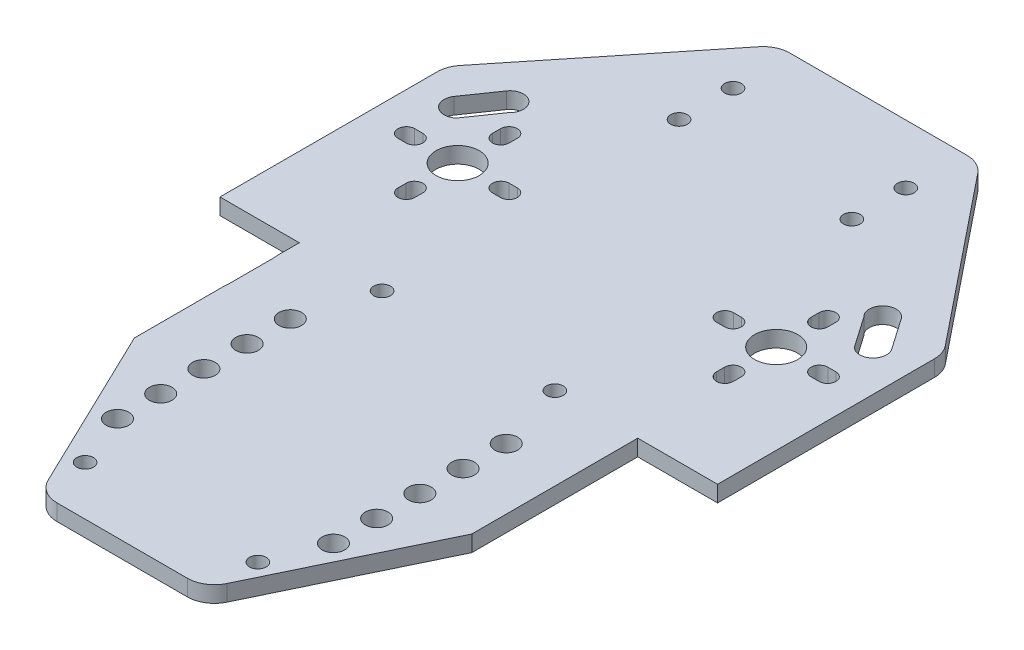
SolidWorks part; units mm, degrees
material "Thornel Mat VMA"
ref_plane "Front Plane" through (0, 0, 0) normal (0, 0, 1) x (1, 0, 0)
ref_plane "Top Plane" through (0, 0, 0) normal (0, 1, 0) x (1, 0, 0)
ref_plane "Right Plane" through (0, 0, 0) normal (1, 0, 0) x (0, 0, -1)
sketch "Sketch1" plane through (0, 0, 0) normal (0, 1, 0) x (1, 0, 0)
  line L0 (0, 0) -> (0, -27.5) construction
  line L1 (0, 0) -> (121.6069, 0) construction
  line L2 (37.5, 0) -> (39, 0) construction
  line L3 (37.5, 1.55) -> (39, 1.55)
  line L4 (37.5, -1.55) -> (39, -1.55)
  line L5 (29.5, -8) -> (29.5, -9.5) construction
  line L6 (31.05, -8) -> (31.05, -9.5)
  line L7 (27.95, -8) -> (27.95, -9.5)
  line L8 (21.5, 0) -> (20, 0) construction
  line L9 (21.5, -1.55) -> (20, -1.55)
  line L10 (21.5, 1.55) -> (20, 1.55)
  line L11 (29.5, 8) -> (29.5, 9.5) construction
  line L12 (27.95, 8) -> (27.95, 9.5)
  line L13 (31.05, 8) -> (31.05, 9.5)
  line L14 (20, -72.5) -> (20, -64.5) construction
  line L19 (-29.5, 8) -> (-29.5, 9.5) construction
  line L20 (-27.95, 8) -> (-27.95, 9.5)
  line L21 (-31.05, 8) -> (-31.05, 9.5)
  line L22 (-21.5, 0) -> (-20, 0) construction
  line L23 (-21.5, -1.55) -> (-20, -1.55)
  line L24 (-21.5, 1.55) -> (-20, 1.55)
  line L25 (-29.5, -8) -> (-29.5, -9.5) construction
  line L26 (-31.05, -8) -> (-31.05, -9.5)
  line L27 (-27.95, -8) -> (-27.95, -9.5)
  line L28 (-37.5, 0) -> (-39, 0) construction
  line L29 (-37.5, 1.55) -> (-39, 1.55)
  line L30 (-37.5, -1.55) -> (-39, -1.55)
  line L31 (-31.3246, -40.5321) -> (-31.3246, -32.4375)
  line L34 (-38.4806, -33.6183) -> (-38.4806, -40.5321)
  line L35 (31.3246, -40.5321) -> (31.3246, -32.4375)
  line L36 (38.4806, -33.6183) -> (38.4806, -40.5321)
  line L37 (-36.8266, 7.1221) -> (-32.8384, 12.8748)
  line L38 (29.5, 0) -> (50.8627, -25.4591) construction
  line L41 (46, 48.4159) -> (-46, 48.4159)
  line L44 (46, 48.4159) -> (46.1488, -91.633)
  line L47 (46.1488, -91.633) -> (-46.1487, -91.584)
  line L50 (-46, 48.4159) -> (-46.1487, -91.584)
  line L53 (-36.5402, 16.1211) -> (-40.5285, 10.3684)
  line L59 (-959, -57) -> (49041, -57) construction
  line L63 (36.8266, 7.1221) -> (32.8384, 12.8748)
  line L64 (36.5402, 16.1211) -> (40.5285, 10.3684)
  circle A0 centre (29.5, 0) radius 4
  arc A1 (37.5, 1.55) -> (37.5, -1.55) centre (37.5, 0) ccw
  arc A2 (39, -1.55) -> (39, 1.55) centre (39, 0) ccw
  arc A3 (31.05, -8) -> (27.95, -8) centre (29.5, -8) ccw
  arc A4 (27.95, -9.5) -> (31.05, -9.5) centre (29.5, -9.5) ccw
  arc A5 (21.5, -1.55) -> (21.5, 1.55) centre (21.5, 0) ccw
  arc A6 (20, 1.55) -> (20, -1.55) centre (20, 0) ccw
  arc A7 (27.95, 8) -> (31.05, 8) centre (29.5, 8) ccw
  arc A8 (31.05, 9.5) -> (27.95, 9.5) centre (29.5, 9.5) ccw
  circle A13 centre (-29.5, 0) radius 4
  arc A14 (-27.95, 8) -> (-31.05, 8) centre (-29.5, 8) cw
  arc A15 (-31.05, 9.5) -> (-27.95, 9.5) centre (-29.5, 9.5) cw
  arc A16 (-21.5, -1.55) -> (-21.5, 1.55) centre (-21.5, 0) cw
  arc A17 (-20, 1.55) -> (-20, -1.55) centre (-20, 0) cw
  arc A18 (-31.05, -8) -> (-27.95, -8) centre (-29.5, -8) cw
  arc A19 (-27.95, -9.5) -> (-31.05, -9.5) centre (-29.5, -9.5) cw
  arc A20 (-37.5, 1.55) -> (-37.5, -1.55) centre (-37.5, 0) cw
  arc A21 (-39, -1.55) -> (-39, 1.55) centre (-39, 0) cw
  circle A22 centre (16, 27.5) radius 1.55
  circle A23 centre (16, -27.5) radius 1.55
  circle A24 centre (-16, -27.5) radius 1.55
  circle A25 centre (-16, 27.5) radius 1.55
  circle A76 centre (-16, 37.5) radius 1.55
  circle A77 centre (16, 37.5) radius 1.55
  circle A78 centre (20, -72.5) radius 2.1
  circle A79 centre (-20, -72.5) radius 2.1
  circle A83 centre (-20, -40.5) radius 2.1
  circle A84 centre (20, -40.5) radius 2.1
  circle A85 centre (20, -64.5) radius 2.1
  circle A86 centre (-20, -64.5) radius 2.1
  circle A87 centre (20, -56.5) radius 2.1
  circle A88 centre (-20, -56.5) radius 2.1
  circle A89 centre (20, -48.5) radius 2.1
  circle A90 centre (-20, -48.5) radius 2.1
  circle A91 centre (-16, -82.5) radius 1.55
  circle A92 centre (16, -82.5) radius 1.55
  arc A93 (-38.4806, -40.5321) -> (-31.3246, -40.5321) centre (-34.9026, -40.5321) ccw
  arc A94 (-31.3246, -32.4375) -> (-38.4806, -33.6183) centre (-35, -32.4375) ccw
  arc A95 (38.4806, -40.5321) -> (31.3246, -40.5321) centre (34.9026, -40.5321) cw
  arc A96 (31.3246, -32.4375) -> (38.4806, -33.6183) centre (35, -32.4375) cw
  arc A103 (-40.5285, 10.3684) -> (-36.8266, 7.1221) centre (-38.4922, 8.9566) ccw
  arc A106 (-36.5402, 16.1211) -> (-32.8384, 12.8748) centre (-34.5039, 14.7093) cw
  arc A107 (36.5402, 16.1211) -> (32.8384, 12.8748) centre (34.5039, 14.7093) ccw
  arc A108 (40.5285, 10.3684) -> (36.8266, 7.1221) centre (38.4922, 8.9566) cw
  point P8 (38.25, 0)
  point P18 (29.5, -8.75)
  point P25 (20.75, 0)
  point P32 (29.5, 8.75)
  point P37 (29.5, 0)
  point P51 (0, 32.5)
  point P55 (-29.5, 8.75)
  point P62 (-20.75, 0)
  point P69 (-29.5, -8.75)
  point P76 (-38.25, 0)
  dimension "D1" = 8
  dimension "D2" = 1.55
  dimension "D4" = 8
  dimension "D5" = 4
  dimension "D6" = 92
  dimension "D7" = 140
  dimension "D8" = 2
  dimension "D9" = 59
  dimension "D10" = 3.1
  dimension "D11" = 40
  dimension "D12" = 27.5
  dimension "D13" = 8
  dimension "D15" = 7
  dimension "D27" = 4.2
  dimension "D28" = 100
  dimension "D3" = 1.5
  dimension "D14" = 35
  dimension "D16" = 7
  dimension "D23" = 50
extrude "Boss-Extrude1" [suppressed] add sketch "Sketch1" along normal blind 3
sketch "草图7" [suppressed] plane through (0, 0, 0) normal (0, 1, 0) x (1, 0, 0)
  line L0 (0, 0) -> (0, -97.058) construction
  line L1 (-27.95, -9.5) -> (-27.95, -8) construction
  line L2 (22.2054, 32.5) -> (-23.2593, 32.5) construction
  line L3 (-31.05, -8) -> (-31.05, -9.5) construction
  line L4 (-37.5, 1.55) -> (-39, 1.55)
  line L5 (-39, -1.55) -> (-37.5, -1.55)
  line L6 (-37.5, 1.55) -> (-39, 1.55)
  line L7 (-39, -1.55) -> (-37.5, -1.55)
  line L8 (-27.95, 8) -> (-27.95, 9.5)
  line L9 (-31.05, 9.5) -> (-31.05, 8)
  line L10 (-27.95, 8) -> (-27.95, 9.5)
  line L11 (-31.05, 9.5) -> (-31.05, 8)
  line L12 (-21.5, -1.55) -> (-20, -1.55)
  line L13 (-20, 1.55) -> (-21.5, 1.55)
  line L14 (-21.5, -1.55) -> (-20, -1.55)
  line L15 (-20, 1.55) -> (-21.5, 1.55)
  line L16 (-27.95, -9.5) -> (-27.95, -8)
  line L17 (-31.05, -8) -> (-31.05, -9.5)
  line L20 (37.5, -1.55) -> (39, -1.55)
  line L21 (39, 1.55) -> (37.5, 1.55)
  line L22 (37.5, -1.55) -> (39, -1.55)
  line L23 (39, 1.55) -> (37.5, 1.55)
  line L24 (27.95, -8) -> (27.95, -9.5)
  line L25 (31.05, -9.5) -> (31.05, -8)
  line L26 (27.95, -8) -> (27.95, -9.5)
  line L27 (31.05, -9.5) -> (31.05, -8)
  line L28 (21.5, 1.55) -> (20, 1.55)
  line L29 (20, -1.55) -> (21.5, -1.55)
  line L30 (21.5, 1.55) -> (20, 1.55)
  line L31 (20, -1.55) -> (21.5, -1.55)
  line L32 (31.05, 8) -> (31.05, 9.5)
  line L33 (27.95, 9.5) -> (27.95, 8)
  line L34 (31.05, 8) -> (31.05, 9.5)
  line L35 (27.95, 9.5) -> (27.95, 8)
  circle A0 centre (29.5, 0) radius 4 construction
  circle A1 centre (29.5, 0) radius 4
  circle A3 centre (-20, -72.5) radius 1.55
  circle A4 centre (-29.5, 0) radius 4
  circle A5 centre (-29.5, 0) radius 4
  circle A6 centre (16, 27.5) radius 1.55
  circle A7 centre (16, 27.5) radius 1.55
  circle A8 centre (-16, 27.5) radius 1.55
  circle A9 centre (-16, 27.5) radius 1.55
  circle A12 centre (16, 37.5) radius 1.55
  circle A13 centre (-16, 37.5) radius 1.55
  circle A14 centre (-16, -27.5) radius 1.55
  circle A15 centre (20, -72.5) radius 1.55
  arc A16 (-31.05, -9.5) -> (-27.95, -9.5) centre (-29.5, -9.5) ccw construction
  arc A18 (-37.5, -1.55) -> (-37.5, 1.55) centre (-37.5, 0) ccw
  arc A19 (-39, 1.55) -> (-39, -1.55) centre (-39, 0) ccw
  arc A20 (-37.5, -1.55) -> (-37.5, 1.55) centre (-37.5, 0) ccw
  arc A21 (-39, 1.55) -> (-39, -1.55) centre (-39, 0) ccw
  arc A23 (-27.95, -8) -> (-31.05, -8) centre (-29.5, -8) ccw construction
  arc A24 (-31.05, 8) -> (-27.95, 8) centre (-29.5, 8) ccw
  arc A25 (-27.95, 9.5) -> (-31.05, 9.5) centre (-29.5, 9.5) ccw
  arc A26 (-31.05, 8) -> (-27.95, 8) centre (-29.5, 8) ccw
  arc A27 (-27.95, 9.5) -> (-31.05, 9.5) centre (-29.5, 9.5) ccw
  arc A28 (-21.5, 1.55) -> (-21.5, -1.55) centre (-21.5, 0) ccw
  arc A29 (-20, -1.55) -> (-20, 1.55) centre (-20, 0) ccw
  arc A30 (-21.5, 1.55) -> (-21.5, -1.55) centre (-21.5, 0) ccw
  arc A31 (-20, -1.55) -> (-20, 1.55) centre (-20, 0) ccw
  arc A32 (-31.05, -9.5) -> (-27.95, -9.5) centre (-29.5, -9.5) ccw
  arc A33 (-27.95, -8) -> (-31.05, -8) centre (-29.5, -8) ccw
  circle A34 centre (16, -27.5) radius 1.55
  arc A36 (37.5, 1.55) -> (37.5, -1.55) centre (37.5, 0) ccw
  arc A37 (39, -1.55) -> (39, 1.55) centre (39, 0) ccw
  arc A38 (37.5, 1.55) -> (37.5, -1.55) centre (37.5, 0) ccw
  arc A39 (39, -1.55) -> (39, 1.55) centre (39, 0) ccw
  arc A40 (31.05, -8) -> (27.95, -8) centre (29.5, -8) ccw
  arc A41 (27.95, -9.5) -> (31.05, -9.5) centre (29.5, -9.5) ccw
  arc A42 (31.05, -8) -> (27.95, -8) centre (29.5, -8) ccw
  arc A43 (27.95, -9.5) -> (31.05, -9.5) centre (29.5, -9.5) ccw
  arc A44 (21.5, -1.55) -> (21.5, 1.55) centre (21.5, 0) ccw
  arc A45 (20, 1.55) -> (20, -1.55) centre (20, 0) ccw
  arc A46 (21.5, -1.55) -> (21.5, 1.55) centre (21.5, 0) ccw
  arc A47 (20, 1.55) -> (20, -1.55) centre (20, 0) ccw
  arc A48 (27.95, 8) -> (31.05, 8) centre (29.5, 8) ccw
  arc A49 (31.05, 9.5) -> (27.95, 9.5) centre (29.5, 9.5) ccw
  arc A50 (27.95, 8) -> (31.05, 8) centre (29.5, 8) ccw
  arc A51 (31.05, 9.5) -> (27.95, 9.5) centre (29.5, 9.5) ccw
  dimension "D4" = 3.1
  dimension "D6" = 20
  dimension "D7" = 5
  dimension "D9" = 3.1
  dimension "D16" = 32
  dimension "D17" = 55
  dimension "D5" = 100
  dimension "D8" = 0
  dimension "D1" = 0
  dimension "D2" = 0
  dimension "D3" = 0
  dimension "D10" = 0
  dimension "D11" = 0
  dimension "D12" = 0
  dimension "D13" = 0
  dimension "D14" = 0
  dimension "D15" = 0
extrude "凸台-拉伸1" add sketch "Sketch1<2>" along normal blind 3 contours L41 L50 L47 L44 A79 A78 A23 A22 A0 A2 L4 A1 L3 A4 L7 A3 L6 A6 L10 A5 L9 A8 L13 A7 L12 A13 L21 A15 L20 A14 L24 A17 L23 A16 region at (0.0029, 0, 21.6938)
sketch "Sketch1<2>" plane through (0, 0, 0) normal (0, 1, 0) x (1, 0, 0) same geometry as "Sketch1"
sketch "草图8" plane through (0, 0, 0) normal (0, 1, 0) x (1, 0, 0)
  line L0 (-11.1069, -100.1389) -> (-60.5812, 2.6993)
  line L1 (-60.5812, 2.6993) -> (-60.5812, -100.1389)
  line L2 (-60.5812, -100.1389) -> (-11.1069, -100.1389)
  line L3 (0, -21.5721) -> (0, 8.1084) construction
  line L4 (60.5812, -100.1389) -> (11.1069, -100.1389)
  line L5 (60.5812, 2.6993) -> (60.5812, -100.1389)
  line L6 (11.1069, -100.1389) -> (60.5812, 2.6993)
  line L7 (-55.5478, 2.6866) -> (-14.4304, 53.8253)
  line L8 (-14.4304, 53.8253) -> (-55.5478, 53.8253)
  line L9 (-55.5478, 53.8253) -> (-55.5478, 2.6866)
  line L10 (55.5478, 53.8253) -> (55.5478, 2.6866)
  line L11 (14.4304, 53.8253) -> (55.5478, 53.8253)
  line L12 (55.5478, 2.6866) -> (14.4304, 53.8253)
  line L13 (-46.0806, -27.4419) -> (-31.3889, -27.4419)
  line L14 (-46, 48.4159) -> (-46.1487, -91.584) construction
  line L15 (-31.3889, -27.4419) -> (-31.3889, -57.9803)
  line L16 (46.0806, -27.4419) -> (31.2972, -27.4419)
  line L17 (31.2972, -27.4419) -> (31.2972, -58.171)
  line L18 (-31.3246, -40.5321) -> (-31.3246, -32.4375) construction
  line L19 (-31.3246, -40.5321) -> (-31.3246, -32.4375)
extrude "切除-拉伸1" cut sketch "草图8" along normal through all contours L1 L2 L0 | L8 L9 L7 | L12 L10 L11 | L6 L4 L5 | L16 L17 L6 | L15 L13 L0 region at (-44.0897, 0, 65.8595) region at (-36.2861, 0, 37.6214) region at (44.0897, 0, 65.8595) region at (36.225, 0, 37.6849) region at (-41.842, 0, -36.779) region at (41.842, 0, -36.779)
fillet "圆角1" radius 5 6 edges at (-15.2146, 1.5, 91.6005) (15.2069, 1.5, 91.6166) (46.036, 1.5, -14.5166) (18.7797, 1.5, -48.4159) (-18.7797, 1.5, -48.4159) (-46.036, 1.5, -14.5166)
